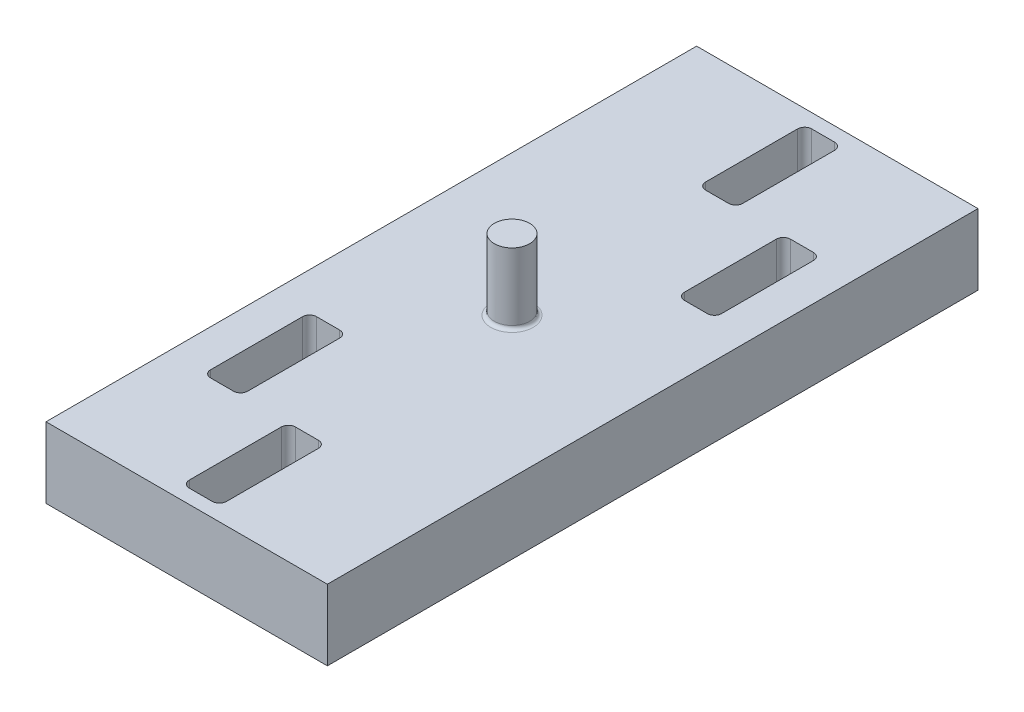
SolidWorks part; units mm, degrees
ref_plane "Front Plane" through (0, 0, 0) normal (0, 0, 1) x (1, 0, 0)
ref_plane "Top Plane" through (0, 0, 0) normal (0, 1, 0) x (1, 0, 0)
ref_plane "Right Plane" through (0, 0, 0) normal (1, 0, 0) x (0, 0, -1)
sketch "10" plane through (0, 0, 0) normal (0, 1, 0) x (1, 0, 0)
  line L0 (-15, 31.5) -> (15, 31.5) construction
  line L1 (-14.8938, 29.7182) -> (14.8938, 33.2818)
  line L2 (-14.8938, 29.7182) -> (-12, 15)
  line L3 (14.8938, 33.2818) -> (12, 48)
  line L4 (-12, 15) -> (0, 15)
  line L5 (12, 48) -> (0, 48)
  line L6 (0, 48) -> (0, 63)
  line L7 (0, 15) -> (0, 0)
  point P4 (0, 31.5)
  point P5 (0, 31.5)
  dimension "D1" = 15
  dimension "D2" = 12
  dimension "D3" = 15
  dimension "D4" = 30
  dimension "D5" = 30
  dimension "D6" = 15
  dimension "D7" = 0
  dimension "D8" = 0
  dimension "D9" = 31.5
sketch "01" plane through (0, 0, 0) normal (0, 1, 0) x (1, 0, 0)
  line L0 (-15, 31.5) -> (15, 31.5) construction
  line L1 (-9.3393, 19.7621) -> (9.3393, 43.2379)
  line L2 (-9.3393, 19.7621) -> (-12, 5)
  line L3 (9.3393, 43.2379) -> (12, 58)
  line L4 (-12, 5) -> (0, 5)
  line L5 (12, 58) -> (0, 58)
  line L6 (0, 58) -> (0, 73)
  line L7 (0, 5) -> (0, -10)
  point P4 (0, 31.5)
  point P5 (0, 31.5)
  dimension "D1" = 30
  dimension "D2" = 15
  dimension "D3" = 12
  dimension "D4" = 15
  dimension "D5" = 30
  dimension "D6" = 0
  dimension "D7" = 41.5
  dimension "D8" = 0
  dimension "D9" = 15
sketch "Sketch2" plane through (0, 0, 0) normal (0, 1, 0) x (1, 0, 0)
  line L1 (-19.8938, 77.5) -> (0, 77.5)
  line L2 (-19.8938, 77.5) -> (-19.8938, -14.5)
  line L3 (-19.8938, -14.5) -> (0, -14.5)
  line L9 (-15, 31.5) -> (15, 31.5) construction
  line L24 (0, 77.5) -> (0, 75.5)
  line L25 (-2.625, 73) -> (-2.625, 63)
  line L26 (0, 75.5) -> (-2.625, 75.5)
  line L27 (-2.625, 75.5) -> (-2.625, 73)
  line L28 (0, 60.5) -> (-2.625, 60.5)
  line L29 (-2.625, 60.5) -> (-2.625, 63)
  line L32 (0, 60.375) -> (0, 2.5)
  line L34 (0, 60.5) -> (0, 60.375)
  line L35 (-2.625, 0) -> (-2.625, -10)
  line L36 (0, 2.5) -> (-2.625, 2.5)
  line L37 (-2.625, 2.5) -> (-2.625, 0)
  line L38 (0, -12.5) -> (-2.625, -12.5)
  line L39 (-2.625, -12.5) -> (-2.625, -10)
  line L41 (0, -12.5) -> (0, -14.5)
  circle A7 centre (-14.8938, 29.7182) radius 5 construction
  circle A19 centre (0, 73) radius 2.625 construction
  circle A21 centre (0, 63) radius 2.625 construction
  circle A22 centre (0, 73) radius 2.5 construction
  circle A23 centre (0, 63) radius 2.5 construction
  circle A24 centre (0, -10) radius 2.625 construction
  circle A25 centre (0, 0) radius 2.625 construction
  circle A26 centre (0, 0) radius 2.5 construction
  circle A27 centre (0, -10) radius 2.5 construction
  dimension "D2" = 5.25
  dimension "D3" = 5.25
  dimension "D4" = 5
  dimension "D5" = 5
  dimension "D8" = 10
  dimension "D7" = 10
  dimension "D9" = 5.25
  dimension "D12" = 5.25
  dimension "D14" = 5
  dimension "D15" = 5
  dimension "D6" = 2
  dimension "D10" = 19.8938
  dimension "D11" = 5
  dimension "D13" = 19.8938
  dimension "D16" = 10
  dimension "D17" = 2
  dimension "D18" = 57.875
extrude "Boss-Extrude1" add sketch "Sketch2" along normal blind 10 contours L2 L3 L41 L38 L39 L35 L37 L36 L32 L34 L28 L29 L25 L27 L26 L24 L1
fillet "Fillet2" radius 1 4 edges at (-2.625, 5, 12.5) (-2.625, 5, -2.5) (-2.625, 5, -60.5) (-2.625, 5, -75.5)
mirror "Mirror1" of "Fillet2", "Boss-Extrude1"
sketch "Sketch4" plane through (0, 0, 0) normal (0, 1, 0) x (1, 0, 0)
  line L0 (-14.625, 15) -> (-14.625, 5)
  line L1 (-9.375, 15) -> (-9.375, 5)
  line L2 (-12, 2.5) -> (-9.375, 2.5)
  line L3 (-9.375, 2.5) -> (-9.375, 5)
  line L4 (-12, 2.5) -> (-14.625, 2.5)
  line L5 (-14.625, 2.5) -> (-14.625, 5)
  line L6 (-12, 17.5) -> (-9.375, 17.5)
  line L7 (-9.375, 17.5) -> (-9.375, 15)
  line L9 (-12, 17.5) -> (-14.625, 17.5)
  line L10 (-14.625, 17.5) -> (-14.625, 15)
  line L12 (9.375, 58) -> (9.375, 48)
  line L13 (14.625, 58) -> (14.625, 48)
  line L16 (12, 60.5) -> (9.375, 60.5)
  line L17 (9.375, 60.5) -> (9.375, 58)
  line L19 (12, 60.5) -> (14.625, 60.5)
  line L20 (14.625, 60.5) -> (14.625, 58)
  line L21 (12, 45.5) -> (14.625, 45.5)
  line L22 (14.625, 45.5) -> (14.625, 48)
  line L23 (12, 45.5) -> (9.375, 45.5)
  line L24 (9.375, 45.5) -> (9.375, 48)
  circle A0 centre (-12, 5) radius 2.625 construction
  circle A1 centre (-12, 15) radius 2.625 construction
  circle A14 centre (-12, 15) radius 2.5 construction
  circle A15 centre (-12, 5) radius 2.5 construction
  circle A16 centre (12, 48) radius 2.625 construction
  circle A17 centre (12, 48) radius 2.5 construction
  circle A18 centre (12, 58) radius 2.5 construction
  circle A19 centre (12, 58) radius 2.625 construction
  dimension "D1" = 5.25
  dimension "D2" = 5
extrude "Cut-Extrude1" cut sketch "Sketch4" along normal through all
fillet "Fillet3" radius 1 8 edges at (9.375, 5, -45.5) (14.625, 5, -45.5) (9.375, 5, -60.5) (14.625, 5, -60.5) (-14.625, 5, -2.5) (-9.375, 5, -2.5) (-9.375, 5, -17.5) (-14.625, 5, -17.5)
sketch "Sketch5" plane through (0, 10, 0) normal (0, 1, 0) x (1, 0, 0)
  line L0 (-14.8938, 29.7182) -> (14.8938, 33.2818) construction
  circle A0 centre (0, 31.5) radius 2.5
  dimension "D1" = 5
extrude "Boss-Extrude2" add sketch "Sketch5" along normal blind 10
fillet "Fillet1" radius 0.5 1 edges at (0, 10, -34)
